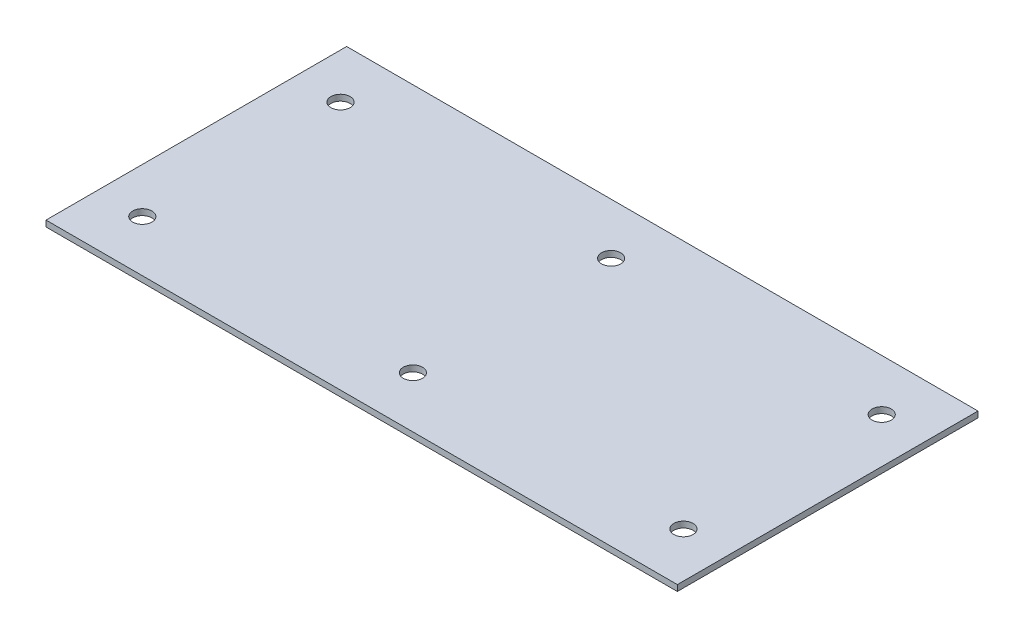
SolidWorks part; units mm, degrees
ref_plane "Спереди" through (0, 0, 0) normal (0, 0, 1) x (1, 0, 0)
ref_plane "Сверху" through (0, 0, 0) normal (0, 1, 0) x (1, 0, 0)
ref_plane "Справа" through (0, 0, 0) normal (1, 0, 0) x (0, 0, -1)
sketch "Эскиз1" plane through (0, 0, 0) normal (0, 1, 0) x (1, 0, 0)
  line L0 (195, 17.0342) -> (15, 17.0342) construction
  line L5 (0, 0) -> (210, 0)
  line L6 (0, 0) -> (0, 100)
  line L7 (0, 100) -> (210, 100)
  line L8 (210, 0) -> (210, 100)
  line L9 (210, 50) -> (0, 50) construction
  circle A0 centre (15, 17.0342) radius 3.2
  circle A1 centre (195, 17.0342) radius 3.2
  circle A2 centre (105, 17.0342) radius 3.2
  circle A3 centre (15, 82.9658) radius 3.2
  circle A4 centre (105, 82.9658) radius 3.2
  circle A5 centre (195, 82.9658) radius 3.2
  dimension "D1" = 210
  dimension "D2" = 100
extrude "Бобышка-Вытянуть1" add sketch "Эскиз1" along normal blind 2
